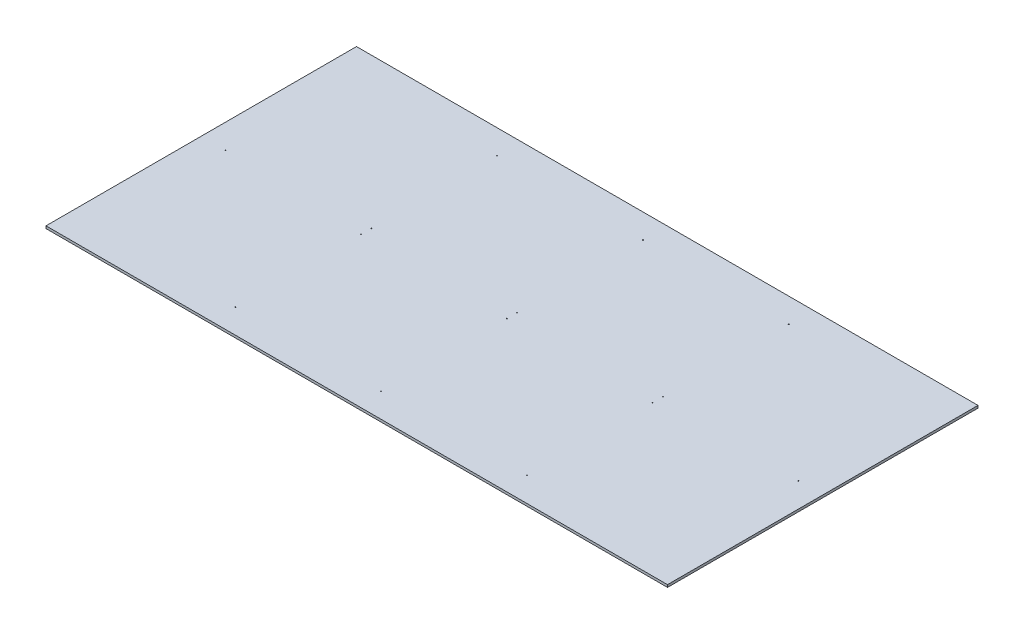
SolidWorks part; units mm, degrees
material "E-Glass Fiber"
ref_plane "Front Plane" through (0, 0, 0) normal (0, 0, 1) x (1, 0, 0)
ref_plane "Top Plane" through (0, 0, 0) normal (0, 1, 0) x (1, 0, 0)
ref_plane "Right Plane" through (0, 0, 0) normal (1, 0, 0) x (0, 0, -1)
other "Center of Mass"
sketch "Sketch1" plane through (0, 0, 0) normal (0, 1, 0) x (1, 0, 0)
  line L1 (-127.9, -63.9) -> (127.9, -63.9)
  line L2 (-127.9, -63.9) -> (-127.9, 63.9)
  line L3 (-127.9, 63.9) -> (127.9, 63.9)
  line L4 (127.9, -63.9) -> (127.9, 63.9)
  line L5 (-127.9, -63.9) -> (127.9, 63.9) construction
  line L6 (-127.9, 63.9) -> (127.9, -63.9) construction
  point P0 (0, 0)
  dimension "D1" = 127.8
  dimension "D2" = 255.8
extrude "Boss-Extrude1" add sketch "Sketch1" along normal blind 1 contours L2 L1 L4 L3
sketch "Sketch2" plane through (0, 1, 0) normal (0, 1, 0) x (1, 0, 0)
  line L0 (-127.9, -63.9) -> (-127.9, 63.9) construction
  line L1 (-127.9, -63.9) -> (127.9, -63.9) construction
  line L2 (-127.9, 0) -> (127.9, 0) construction
  line L4 (-127.9, 63.9) -> (127.9, 63.9) construction
  line L5 (127.9, -63.9) -> (127.9, 63.9) construction
  line L6 (0, 63.9) -> (0, -63.9) construction
  point P0 (-117.875, 0)
  point P10 (-60, 2.125)
  point P11 (-60, 53.875)
  point P17 (117.875, 0)
  point P20 (60, 2.125)
  point P21 (60, 53.875)
  point P22 (0, 2.125)
  point P41 (0, 53.875)
  point P44 (60, -2.125)
  point P45 (60, -53.875)
  point P46 (0, -2.125)
  point P47 (0, -53.875)
  point P48 (-60, -2.125)
  point P49 (-60, -53.875)
  dimension "D1" = 10.025
  dimension "D2" = 63.9
  dimension "D3" = 67.9
  dimension "D4" = 2.125
  dimension "D5" = 10.025
  dimension "D6" = 67.9
  dimension "D7" = 2.125
  dimension "D8" = 10.025
hole_wizard "Ø0.35 (0.35) Diameter Hole1" positions "Sketch2" profile "Sketch3" hole size "Ø0.35" standard "ANSI Metric" end condition through all
sketch "Sketch3" plane through (-117.875, 1, 0) normal (1, 0, 0) x (0, 0, 1)
  line L0 (0, 0) -> (0, 1)
  line L1 (0, 1) -> (0.175, 1)
  line L2 (0.175, 1) -> (0.175, 0)
  line L5 (0.175, 0) -> (0, 0)
  line L11 (0, -6.35) -> (0, 107.95) construction
  dimension "Thru Hole Dia." = 0.35
  dimension "Thru Hole Depth" = 1
equation "\"H\"=63.9"
